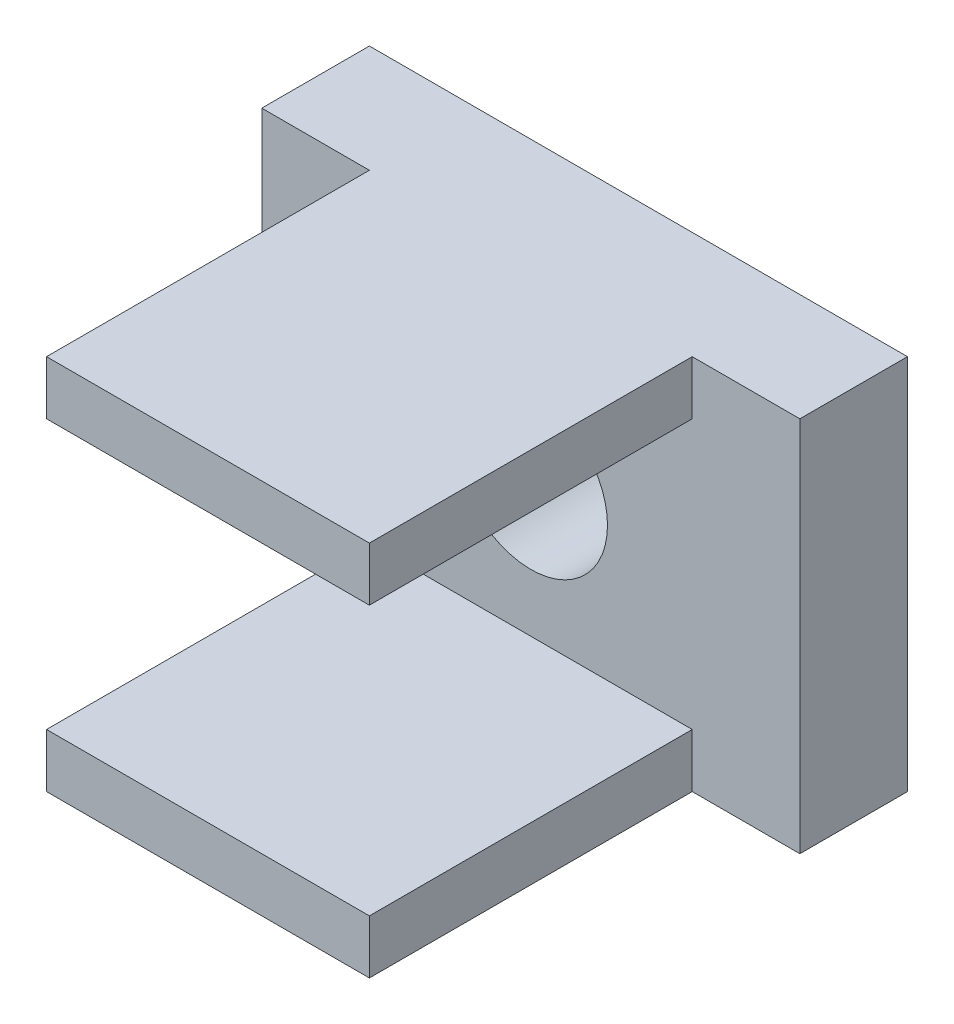
SolidWorks part; units mm, degrees
ref_plane "Front Plane" through (0, 0, 0) normal (0, 0, 1) x (1, 0, 0)
ref_plane "Top Plane" through (0, 0, 0) normal (0, 1, 0) x (1, 0, 0)
ref_plane "Right Plane" through (0, 0, 0) normal (1, 0, 0) x (0, 0, -1)
sketch "Sketch1" plane through (0, 0, 0) normal (0, 0, 1) x (1, 0, 0)
  line L1 (-5, -3.5) -> (5, -3.5)
  line L2 (-5, -3.5) -> (-5, 3.5)
  line L3 (-5, 3.5) -> (5, 3.5)
  line L4 (5, -3.5) -> (5, 3.5)
  line L5 (-5, -3.5) -> (5, 3.5) construction
  line L6 (-5, 3.5) -> (5, -3.5) construction
  point P0 (0, 0)
  dimension "D1" = 10
  dimension "D2" = 7
extrude "Boss-Extrude1" add sketch "Sketch1" along normal mid plane 2
sketch "Sketch2" plane through (0, 0, 1) normal (0, 0, 1) x (1, 0, 0)
  circle A0 centre (0, 0) radius 1.425
  dimension "D1" = 2.85
extrude "Cut-Extrude1" cut sketch "Sketch2" against normal through all
sketch "Sketch3" plane through (0, 0, 1) normal (0, 0, 1) x (1, 0, 0)
  line L0 (5, 3.5) -> (-5, 3.5) construction
  line L1 (-3, 2.5) -> (3, 2.5)
  line L2 (-3, 2.5) -> (-3, 3.5)
  line L3 (-3, 3.5) -> (3, 3.5)
  line L4 (3, 2.5) -> (3, 3.5)
  line L5 (-3, 2.5) -> (3, 3.5) construction
  line L6 (-3, 3.5) -> (3, 2.5) construction
  line L7 (0, 0) -> (0, 3.5) construction
  point P0 (0, 3)
  point P10 (0, 0)
  dimension "D1" = 1
  dimension "D2" = 6
extrude "Boss-Extrude2" add sketch "Sketch3" along normal blind 6
mirror "Mirror1" about plane through (0, 0, 0) normal (0, 1, 0) of "Boss-Extrude2"
